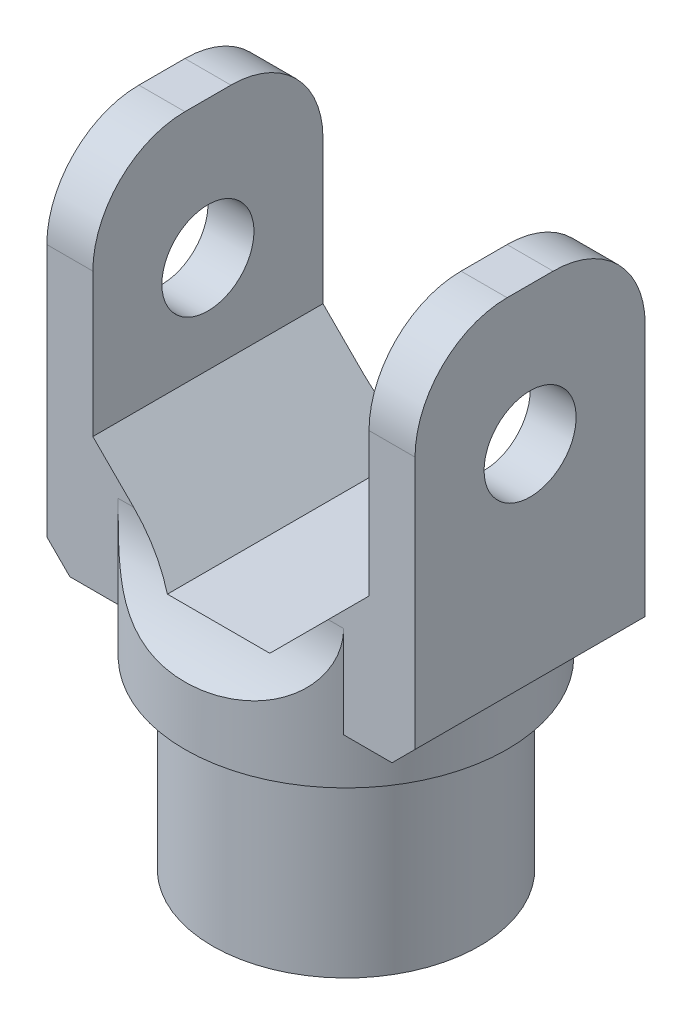
SolidWorks part; units mm, degrees
ref_plane "Front Plane" through (0, 0, 0) normal (0, 0, 1) x (1, 0, 0)
ref_plane "Top Plane" through (0, 0, 0) normal (0, 1, 0) x (1, 0, 0)
ref_plane "Right Plane" through (0, 0, 0) normal (1, 0, 0) x (0, 0, -1)
sketch "Sketch2" plane through (0, 0, 0) normal (0, 1, 0) x (1, 0, 0)
  circle A0 centre (0, 0) radius 15.875
  circle A1 centre (0, 0) radius 18.415
  dimension "D1" = 31.75
  dimension "D2" = 36.83
extrude "Boss-Extrude1" add sketch "Sketch2" along normal blind 25.4
sketch "Sketch3" plane through (0, 25.4, 0) normal (0, 1, 0) x (1, 0, 0)
  circle A0 centre (0, 0) radius 22.225
extrude "Boss-Extrude2" add sketch "Sketch3" along normal blind 6.35
sketch "Sketch5" plane through (0, 31.75, 0) normal (0, 1, 0) x (1, 0, 0)
  line L1 (-25.4, -15.875) -> (25.4, -15.875)
  line L2 (-25.4, -15.875) -> (-25.4, 15.875)
  line L3 (-25.4, 15.875) -> (25.4, 15.875)
  line L4 (25.4, -15.875) -> (25.4, 15.875)
  line L5 (-25.4, -15.875) -> (25.4, 15.875) construction
  line L6 (-25.4, 15.875) -> (25.4, -15.875) construction
  point P0 (0, 0)
  dimension "D1" = 31.75
  dimension "D2" = 50.8
extrude "Boss-Extrude3" add sketch "Sketch5" along normal blind 50.8
sketch "Sketch7" plane through (0, 0, 15.875) normal (0, 0, 1) x (1, 0, 0)
  line L0 (-25.4, 82.55) -> (-19.05, 82.55)
  line L1 (-25.4, 82.55) -> (25.4, 82.55) construction
  line L2 (-19.05, 82.55) -> (-19.05, 50.0843)
  line L3 (-19.05, 50.0843) -> (-7.0657, 38.1)
  line L4 (-7.0657, 38.1) -> (7.0657, 38.1)
  line L5 (7.0657, 38.1) -> (19.05, 50.0843)
  line L6 (25.4, 82.55) -> (25.4, 31.75) construction
  line L7 (25.4, 61.8776) -> (25.4, 82.55)
  line L8 (19.05, 50.0843) -> (19.05, 82.55)
  line L9 (19.05, 82.55) -> (25.4, 82.55)
  line L10 (-25.4, 82.55) -> (-25.4, 31.75) construction
  line L11 (-22.225, 31.75) -> (22.225, 31.75)
  line L12 (-13.0578, 44.0922) -> (-25.4, 31.75) construction
  line L13 (13.0578, 44.0922) -> (25.4, 31.75) construction
  line L14 (-22.225, 31.75) -> (-25.4, 34.925)
  line L15 (22.225, 31.75) -> (25.4, 34.925)
  line L16 (-25.4, 34.925) -> (-25.4, 82.55)
  line L17 (25.4, 34.925) -> (25.4, 61.8776)
  line L18 (-25.4, 34.925) -> (-25.4, 31.75)
  line L19 (-22.225, 31.75) -> (-25.4, 31.75)
  line L20 (22.225, 31.75) -> (25.4, 31.75)
  line L21 (25.4, 31.75) -> (25.4, 34.925)
  line L22 (-19.05, 82.55) -> (19.05, 82.55)
  line M11 (-25.4, 31.75) -> (-15.5543, 31.75)
  line M14 (25.4, 82.55) -> (-25.4, 82.55)
  line M15 (-25.4, 82.55) -> (-25.4, 31.75)
  dimension "D1" = 6.35
  dimension "D2" = 6.35
extrude "Cut-Extrude2" cut sketch "Sketch7" against normal blind 50.8 contours L5 L8 L2 L3 L4 M14 | L14 M11 M15 | L15 L20 L21 region at (0, 62.0143, 15.875) region at (-24.3417, 32.8083, 15.875)
fillet "Fillet1" radius 12.7 4 edges at (-22.225, 82.55, -15.875) (-22.225, 82.55, 15.875) (22.225, 82.55, -15.875) (22.225, 82.55, 15.875)
sketch "Sketch9" plane through (-25.4, 0, 0) normal (-1, 0, 0) x (0, 0, 1)
  line L0 (-15.875, 34.925) -> (15.875, 34.925) construction
  line L1 (15.875, 34.925) -> (15.875, 92.075) construction
  line L2 (15.875, 92.075) -> (-15.875, 92.075) construction
  line L3 (-15.875, 92.075) -> (-15.875, 34.925) construction
  line L5 (-15.875, 69.85) -> (-15.875, 34.925) construction
  line L6 (-3.175, 82.55) -> (3.175, 82.55) construction
  line L7 (-15.875, 63.5) -> (15.875, 63.5) construction
  circle A0 centre (0, 63.5) radius 6.35
  dimension "D1" = 12.7
  dimension "D2" = 19.05
extrude "Cut-Extrude3" cut sketch "Sketch9" against normal through all
fillet "Fillet2" radius 12.7 2 edges at (0, 31.75, 15.875) (0, 31.75, -15.875)
